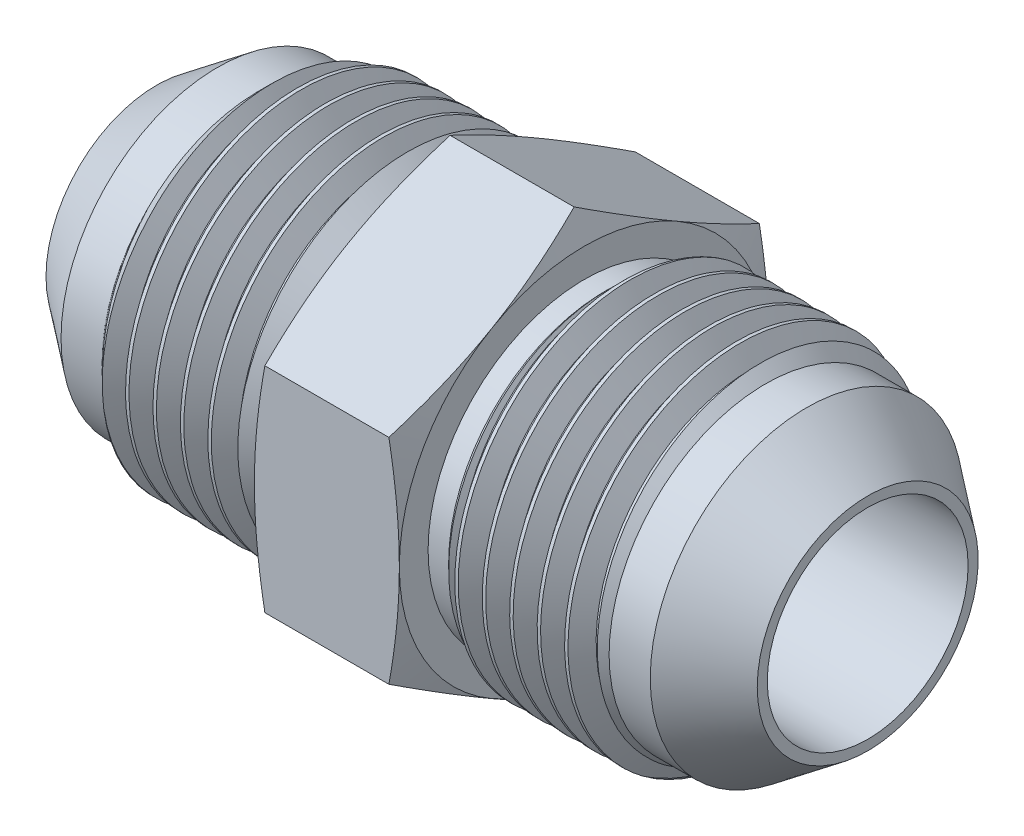
SolidWorks part; units mm, degrees
ref_plane "Front" through (0, 0, 0) normal (0, 0, 1) x (1, 0, 0)
ref_plane "Top" through (0, 0, 0) normal (0, 1, 0) x (1, 0, 0)
ref_plane "Right" through (0, 0, 0) normal (1, 0, 0) x (0, 0, -1)
sketch "Sketch6" plane through (0, 0, 0) normal (0, 0, 1) x (1, 0, 0)
  line L1 (27.432, 13.4937) -> (27.432, -13.4937) construction
  line L2 (-27.432, 0) -> (27.432, 0)
  line L4 (-27.432, 0) -> (-27.432, 13.4937)
  line L5 (-27.432, 13.4937) -> (27.432, 13.4937)
  line L6 (27.432, 0) -> (27.432, 13.4937)
  point P4 (5.588, 0)
  point P6 (-5.588, 0)
  dimension "Straight Dia" = 26.9875
  dimension "Length" = 54.864
  dimension "L1" = 21.844
  dimension "D1" = 21.844
revolve "Revolve3" add sketch "Sketch6" angle 360 about L2
sketch "Sketch14" plane through (-27.432, 0, 0) normal (-1, 0, 0) x (0, 0, 1)
  circle A0 centre (0, 0) radius 13.4938
  circle A2 centre (0, 0) radius 13.4937 construction
curve "Helix/Spiral1" pitch 2.1167 height 56.9807 radius 13.4938 centre (-27.432, 0, 0) axis (1, 0, 0) start towards (0, 1, 0) parameters "Pitch"=2.1167
sketch "Sketch15" plane through (0, 0, 0) normal (0, 0, 1) x (1, 0, 0)
  line L0 (-29.2841, 13.4937) -> (-27.432, 13.4937)
  line L1 (-27.432, 13.4937) -> (-28.2258, 12.1189)
  line L2 (-28.2258, 12.1189) -> (-28.4903, 12.1189)
  line L3 (-28.4903, 12.1189) -> (-29.2841, 13.4937)
  line L4 (-28.358, 12.1189) -> (-28.358, 13.4937) construction
  line L5 (-28.8872, 12.8063) -> (-27.8289, 12.8063) construction
  dimension "D1" = 60
  dimension "D2" = 0.2646
  dimension "D3" = 1.0583
sweep "Cut-Sweep1" cut profiles "Sketch15" path "Helix/Spiral1" align with end faces yes
ref_plane "Plane1" through (-5.588, 0, 0) normal (1, 0, 0) x (0, 0, -1)
sketch "Sketch12" plane through (-5.588, 0, 0) normal (1, 0, 0) x (0, 0, -1)
  line L1 (0, 16.4978) -> (-14.2875, 8.2489)
  line L2 (-14.2875, 8.2489) -> (-14.2875, -8.2489)
  line L3 (-14.2875, -8.2489) -> (0, -16.4978)
  line L4 (0, -16.4978) -> (14.2875, -8.2489)
  line L5 (14.2875, -8.2489) -> (14.2875, 8.2489)
  line L6 (14.2875, 8.2489) -> (0, 16.4978)
  circle A0 centre (0, 0) radius 14.2875 construction
  dimension "Hex" = 28.575
extrude "Extrude1" add sketch "Sketch12" along normal up to vertex (11.176 mm away) up to point (5.588, 0, 0)
sketch "Sketch7" plane through (0, 0, 0) normal (0, 0, 1) x (1, 0, 0)
  line L0 (-27.432, 0) -> (-27.432, 7.747)
  line L2 (-27.432, 7.747) -> (27.432, 7.747)
  line L4 (27.432, 0) -> (27.432, 13.4937) construction
  line L11 (27.432, 7.747) -> (27.432, 0)
  line L12 (27.432, 0) -> (-27.432, 0)
  line L13 (-27.432, 7.747) -> (-27.432, -7.747) construction
  dimension "ID" = 15.494
revolve "Cut-Revolve5" cut sketch "Sketch7" angle 360 about L12
sketch "Sketch10" plane through (0, 0, 0) normal (0, 0, 1) x (1, 0, 0)
  line L0 (-27.432, 13.4937) -> (-27.432, 8.5217)
  line L2 (-27.432, 8.5217) -> (-22.7257, 12.0681)
  line L3 (-22.7257, 12.0681) -> (-19.5507, 12.0681)
  line L4 (-19.5507, 12.0681) -> (-18.1251, 13.4937)
  line L5 (-18.1251, 13.4937) -> (-27.432, 13.4937)
  line L6 (-8.6011, 13.4937) -> (-5.588, 13.4937)
  line L8 (-5.588, 13.4937) -> (-5.588, 12.0681)
  line L9 (-5.588, 12.0681) -> (-7.1755, 12.0681)
  line L11 (-7.1755, 12.0681) -> (-8.6011, 13.4937)
  line L13 (-27.432, 8.5217) -> (-27.432, -8.5217) construction
  line L14 (-27.432, 0) -> (0, 0) construction
  line L15 (-27.432, 0) -> (27.432, 0) construction
  line L16 (-5.588, 16.4978) -> (-5.588, 8.2489) construction
  line L17 (-27.432, 13.4937) -> (27.432, 13.4937) construction
  line L18 (0, 0) -> (0, 16.4978) construction
  line L19 (5.588, 16.4978) -> (-5.588, 16.4978) construction
  line L20 (7.1755, 12.0681) -> (8.6011, 13.4937)
  line L21 (5.588, 12.0681) -> (7.1755, 12.0681)
  line L22 (5.588, 13.4937) -> (5.588, 12.0681)
  line L23 (8.6011, 13.4937) -> (5.588, 13.4937)
  line L24 (18.1251, 13.4937) -> (27.432, 13.4937)
  line L25 (19.5507, 12.0681) -> (18.1251, 13.4937)
  line L26 (22.7257, 12.0681) -> (19.5507, 12.0681)
  line L27 (27.432, 8.5217) -> (22.7257, 12.0681)
  line L28 (27.432, 13.4937) -> (27.432, 8.5217)
  line L29 (-15.7903, -13.4937) -> (-15.7903, 13.4937) construction
  line L30 (0, 0) -> (-15.7903, 0) construction
  point P38 (-15.7903, -13.4937)
  dimension "D1" = 45
  dimension "D2" = 1.5875
  dimension "D3" = 45
  dimension "D4" = 37
  dimension "D5" = 17.0434
  dimension "D6" = 3.175
  dimension "D7" = 0.0508
  dimension "D8" = 11.6417
revolve "Cut-Revolve6" cut sketch "Sketch10" angle 360 about L2
sketch "Sketch16" plane through (-5.588, 0, 0) normal (-1, 0, 0) x (0, 0, 1)
  circle A0 centre (0, 0) radius 14.2875 construction
  circle A1 centre (0, 0) radius 14.2875
extrude "Cut-Extrude1" cut sketch "Sketch16" against normal through all draft 70 flip side to cut
sketch "Sketch17" plane through (5.588, 0, 0) normal (1, 0, 0) x (0, 0, -1)
  circle A1 centre (0, 0) radius 14.2875
  circle A2 centre (0, 0) radius 14.2875
  dimension "D1" = 0
extrude "Cut-Extrude2" cut sketch "Sketch17" against normal through all draft 70 flip side to cut
equation "\"D1@Sketch6\" = \"L1@Sketch6\""
equation "\"D2@Sketch15\" = \"Pitch@Helix/Spiral1\"*.125"
equation "\"D3@Sketch15\" = \"Pitch@Helix/Spiral1\"*.50"
equation "\"D3@Helix/Spiral1\" = \"Length@Sketch6\"+\"Pitch@Helix/Spiral1\""
equation "\"D2@Sketch10\" = \"Pitch@Helix/Spiral1\"*.750"
equation "\"D5@Sketch10\" = \"ID@Sketch7\"*1.1"
equation "\"D6@Sketch10\" = \"Pitch@Helix/Spiral1\"*1.50"
equation "\"D8@Sketch10\" = \"Pitch@Helix/Spiral1\"*5.50"
